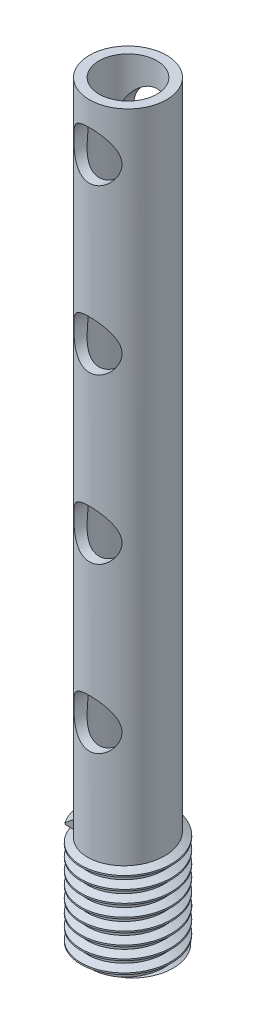
SolidWorks part; units mm, degrees
material "ABS"
ref_plane "Front Plane" through (0, 0, 0) normal (0, 0, 1) x (1, 0, 0)
ref_plane "Top Plane" through (0, 0, 0) normal (0, 1, 0) x (1, 0, 0)
ref_plane "Right Plane" through (0, 0, 0) normal (1, 0, 0) x (0, 0, -1)
sketch "Sketch1" plane through (0, 0, 0) normal (0, 1, 0) x (1, 0, 0)
  circle A0 centre (0, 0) radius 4
  dimension "D1" = 8
extrude "Boss-Extrude1" add sketch "Sketch1" along normal blind 78
shell "Shell1" thickness 2
sketch "Sketch2" plane through (0, 78, 0) normal (0, 1, 0) x (1, 0, 0)
  circle A0 centre (0, 0) radius 3
  dimension "D1" = 6
extrude "Cut-Extrude1" cut sketch "Sketch2" against normal blind 78
sketch "Sketch3" plane through (0, 0, 0) normal (0, 0, 1) x (1, 0, 0)
  line L0 (0, 0) -> (-4, 0) construction
  line L1 (-3, 0) -> (3, 0) construction
  line L2 (-4, 0) -> (4, 0) construction
  circle A0 centre (0, 22) radius 2.5
  circle A1 centre (0, 39) radius 2.5
  circle A2 centre (0, 56) radius 2.5
  circle A3 centre (0, 73) radius 2.5
  dimension "D1" = 5
  dimension "D2" = 5
  dimension "D3" = 5
  dimension "D4" = 5
  dimension "D5" = 22
  dimension "D6" = 17
  dimension "D7" = 17
  dimension "D8" = 17
extrude "Cut-Extrude2" cut sketch "Sketch3" against normal through all both and the other way through all
thread "Thread2" pitch 1.25 method extrude profile "Thread Profile2" start angle 0, offset 2, length 12, pitch 1.25, diameter 8
ref_plane "Plane2" through (4, -2, 0) normal (0, 0, 1) x (1, 0, 0)
sketch "Thread Profile2" plane through (4, -2, 0) normal (0, 0, 1) x (1, 0, 0)
  line L0 (0, 0) -> (0, 1.25) construction
  line L1 (0, 0) -> (0.6766, 0.3906)
  line L2 (0.6766, 0.3906) -> (0.6766, 0.5469)
  line L3 (0.6766, 0.5469) -> (0, 0.9375)
  line L4 (0.6766, 0.4687) -> (0, 0.4687) construction
  line L11 (0, 0) -> (0, 0.9375)
  point P2 (0, 0)
  dimension "Pitch" = 1.25
  dimension "Profile_Angle" = 60
  dimension "Profile_Land" = 0.1562
  dimension "Profile_Height" = 0.6766
sketch "Sketch15" plane through (0, 0, 0) normal (0, -1, 0) x (1, 0, 0)
  circle A0 centre (0, 0) radius 5.1353
extrude "Cut-Extrude3" cut sketch "Sketch15" along normal blind 10
